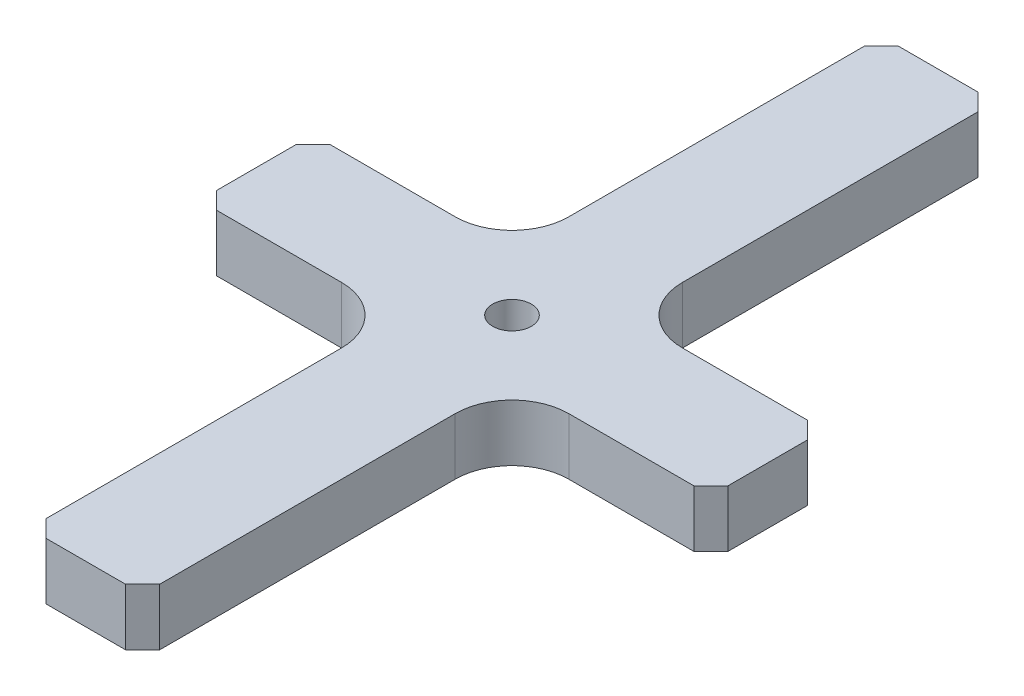
SolidWorks part; units mm, degrees
material "Thornel Mat VMA"
ref_plane "Front Plane" through (0, 0, 0) normal (0, 0, 1) x (1, 0, 0)
ref_plane "Top Plane" through (0, 0, 0) normal (0, 1, 0) x (1, 0, 0)
ref_plane "Right Plane" through (0, 0, 0) normal (1, 0, 0) x (0, 0, -1)
sketch "Sketch2" plane through (0, 0, 0) normal (0, 1, 0) x (1, 0, 0)
  line L0 (0, 0) -> (0, 37.5) construction
  line L1 (-5, 37.5) -> (5, 37.5)
  line L2 (5, 37.5) -> (5, 5)
  line L4 (22.5, 5) -> (5, 5)
  line L5 (22.5, -5) -> (22.5, 5)
  line L6 (-22.5, -5) -> (-22.5, 5)
  line L7 (-22.5, 5) -> (-5, 5)
  line L8 (-5, 37.5) -> (-5, 5)
  line L9 (0, 0) -> (-22.5, 0) construction
  line L10 (22.5, -5) -> (5, -5)
  line L11 (5, -37.5) -> (5, -5)
  line L12 (-5, -37.5) -> (5, -37.5)
  line L13 (-5, -37.5) -> (-5, -5)
  line L14 (-22.5, -5) -> (-5, -5)
  point P12 (22.5, 0)
  dimension "D1" = 5
  dimension "D2" = 37.5
  dimension "D3" = 22.5
  dimension "D4" = 10
extrude "Boss-Extrude1" add sketch "Sketch2" along normal mid plane 5
fillet "Fillet1" radius 5 4 edges at (-5, 0, -5) (5, 0, -5) (5, 0, 5) (-5, 0, 5)
chamfer "Chamfer1" distance 1.5 angle 45 8 edges at (-22.5, 0, 5) (-22.5, 0, -5) (-5, 0, -37.5) (5, 0, -37.5) (22.5, 0, -5) (22.5, 0, 5) (5, 0, 37.5) (-5, 0, 37.5)
hole_wizard "M3 Clearance Hole1" positions "Sketch3" profile "Sketch4" hole size "M3" standard "ANSI Metric"
sketch "Sketch3" plane through (0, 2.5, 0) normal (0, 1, 0) x (1, 0, 0)
  point P0 (0, 0)
sketch "Sketch4" plane through (0, 2.5, 0) normal (1, 0, 0) x (0, 0, 1)
  line L0 (0, 0) -> (0, 6.2215)
  line L1 (0, 6.2215) -> (1.7, 5.2)
  line L2 (1.7, 5.2) -> (1.7, 0)
  line L5 (1.7, 0) -> (0, 0)
  line L10 (0, 6.2215) -> (-1.7, 5.2) construction
  line L11 (0, -6.35) -> (0, 107.95) construction
  dimension "Hole Dia." = 3.4
  dimension "Hole Depth" = 5.2
  dimension "Drill Angle" = 118
